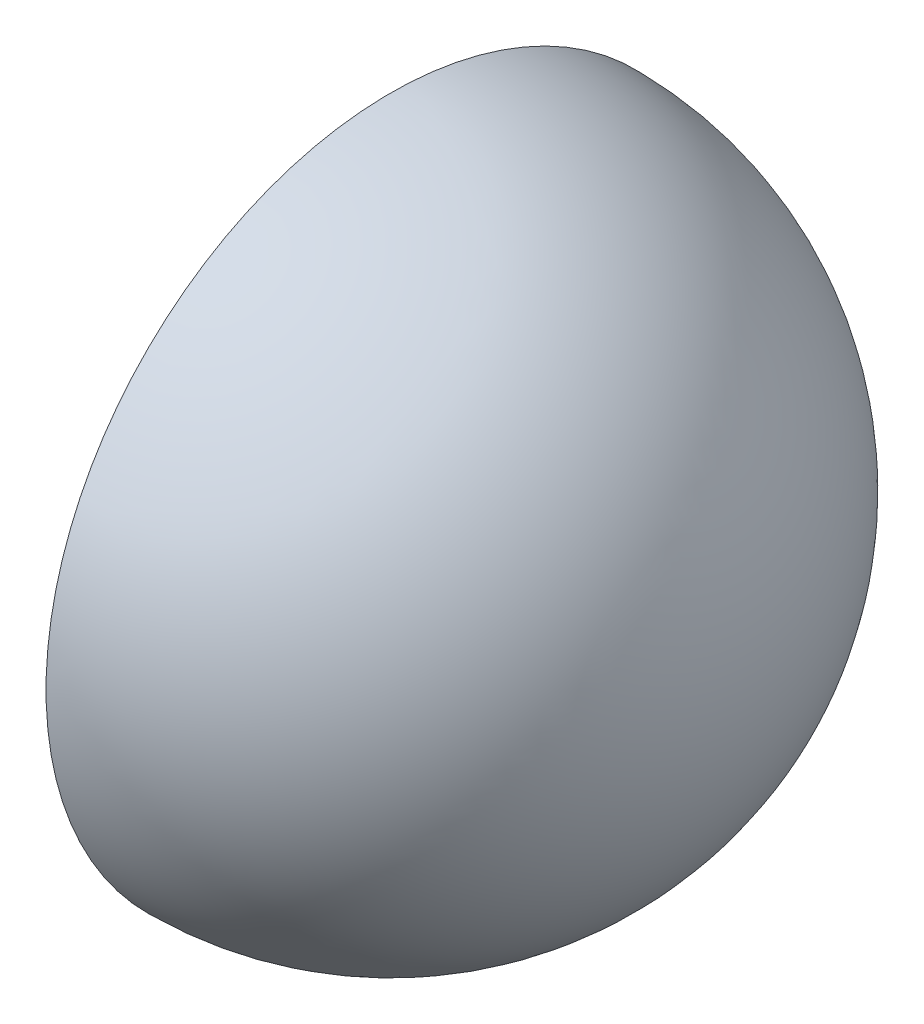
SolidWorks part; units mm, degrees
ref_plane "Front Plane" through (0, 0, 0) normal (0, 0, 1) x (1, 0, 0)
ref_plane "Top Plane" through (0, 0, 0) normal (0, 1, 0) x (1, 0, 0)
ref_plane "Right Plane" through (0, 0, 0) normal (1, 0, 0) x (0, 0, -1)
sketch "Sketch2" plane through (0, 0, 0) normal (1, 0, 0) x (0, 0, -1)
  circle A0 centre (0, 0) radius 25
extrude "Boss-Extrude1" add sketch "Sketch2" along normal blind 25
fillet "Fillet1" radius 25 1 edges at (25, 0, -25)
sketch "Sketch3" plane through (0, 0, 0) normal (-1, 0, 0) x (0, 0, 1)
  circle A0 centre (0, 0) radius 13
extrude "Cut-Extrude1" cut sketch "Sketch3" against normal blind 15
thread "Thread2" pitch 5 method extrude profile "Thread Profile3" start angle 5, offset 4, length 15, pitch 5, diameter 26
ref_plane "Plane3" through (-4, 1.133, -12.9505) normal (0, -0.9962, -0.0872) x (0, 0.0872, -0.9962)
sketch "Thread Profile3" plane through (-4, 1.133, -12.9505) normal (0, -0.9962, -0.0872) x (0, 0.0872, -0.9962)
  line L0 (0, 0) -> (0, 5) construction
  line L11 (0, 0) -> (0, 4.375)
  line L12 (0, 4.375) -> (-2.7063, 2.8125)
  line L13 (-2.7063, 2.8125) -> (-2.7063, 1.5625)
  line L15 (-2.7063, 1.5625) -> (0, 0)
  line L17 (-2.7063, 2.1875) -> (0, 2.1875) construction
  point P2 (0, 0)
  dimension "Pitch" = 5
  dimension "Profile_Angle" = 60
  dimension "Profile_Land" = 1.25
  dimension "Profile_Height" = 2.7063
sketch "Sketch17" plane through (0, 0, 0) normal (-1, 0, 0) x (0, 0, 1)
  line L1 (-15.6031, 15.2854) -> (16.6621, 15.2854)
  line L2 (-15.6031, 15.2854) -> (-15.6031, -15.8502)
  line L3 (-15.6031, -15.8502) -> (16.6621, -15.8502)
  line L4 (16.6621, 15.2854) -> (16.6621, -15.8502)
extrude "Cut-Extrude2" cut sketch "Sketch17" along normal blind 70
